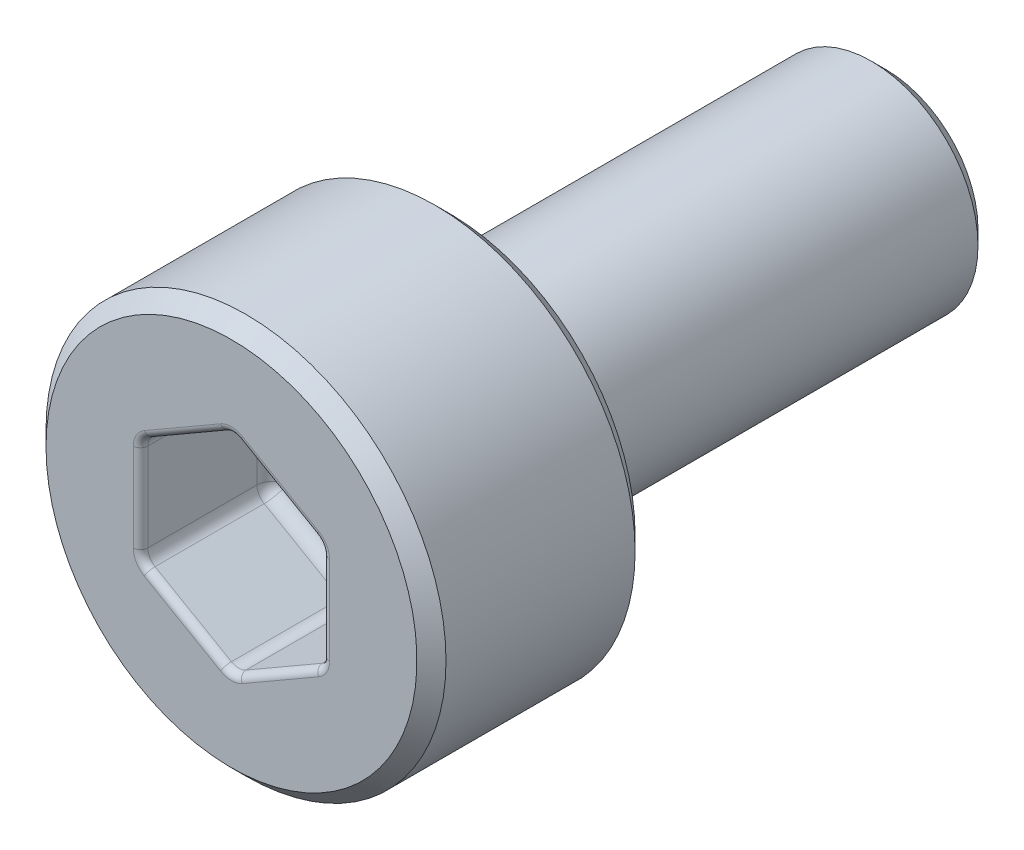
SolidWorks part; units mm, degrees
material "1.4000 (X6Cr13)"
ref_plane "Ebene vorne" through (0, 0, 0) normal (0, 0, 1) x (1, 0, 0)
ref_plane "Ebene oben" through (0, 0, 0) normal (0, 1, 0) x (1, 0, 0)
ref_plane "Ebene rechts" through (0, 0, 0) normal (1, 0, 0) x (0, 0, -1)
sketch "Skizze1" plane through (0, 0, 0) normal (1, 0, 0) x (0, 0, -1)
  line L0 (-21.9199, 0) -> (33.7608, 0) construction
  line L1 (0, 13.9907) -> (0, -9.4798) construction
  line L2 (-3, 0) -> (-3, 2.75)
  line L3 (-3, 2.75) -> (0, 2.75)
  line L4 (0, 2.75) -> (0, 1.465)
  line L5 (0, 1.465) -> (6, 1.465)
  line L6 (6, 1.465) -> (6, 0)
  line L7 (6, 0) -> (-3, 0)
  dimension "D1" = 2.93
  dimension "D2" = 3
  dimension "D3" = 5.5
  dimension "D4" = 6
revolve "Rotation1" add sketch "Skizze1" angle 360 about L0
sketch "Skizze2" plane through (0, 0, 3) normal (0, 0, 1) x (1, 0, 0)
  line L0 (0, 8.6995) -> (0, -7.3778) construction
  line L1 (1.25, -0.7217) -> (1.25, 0.7217)
  line L2 (1.25, 0.7217) -> (0, 1.4434)
  line L3 (0, 1.4434) -> (-1.25, 0.7217)
  line L4 (-1.25, 0.7217) -> (-1.25, -0.7217)
  line L5 (-1.25, -0.7217) -> (0, -1.4434)
  line L6 (0, -1.4434) -> (1.25, -0.7217)
  circle A0 centre (0, 0) radius 1.25 construction
  dimension "D1" = 2.5
extrude "Schnitt-Linear austragen1" cut sketch "Skizze2" against normal blind 1.8
chamfer "Fase1" distance 0.2 angle 45 3 edges at (2.75, 0, 3) (2.75, 0, 0) (1.465, 0, -6)
fillet "Verrundung1" radius 0.2 13 edges at (-0.625, -1.0825, 1.2) (-1.25, 0, 1.2) (-0.625, 1.0825, 1.2) (0.625, 1.0825, 1.2) (1.25, 0, 1.2) (0.625, -1.0825, 1.2) (-1.25, -0.7217, 2.1) (0, -1.4434, 2.1) (1.25, -0.7217, 2.1) (1.25, 0.7217, 2.1) (0, 1.4434, 2.1) (-1.25, 0.7217, 2.1) (1.465, 0, 0)
fillet "Verrundung2" radius 0.1 12 edges at (1.2232, -0.7062, 3) (0.625, -1.0825, 3) (0, -1.4124, 3) (-0.625, -1.0825, 3) (-1.2232, -0.7062, 3) (-1.25, 0, 3) (-1.2232, 0.7062, 3) (-0.625, 1.0825, 3) (0, 1.4124, 3) (0.625, 1.0825, 3) (1.2232, 0.7062, 3) (1.25, 0, 3)
ref_axis "Achse1" through (0, 0, -19.6323) along (0, 0, 1)
